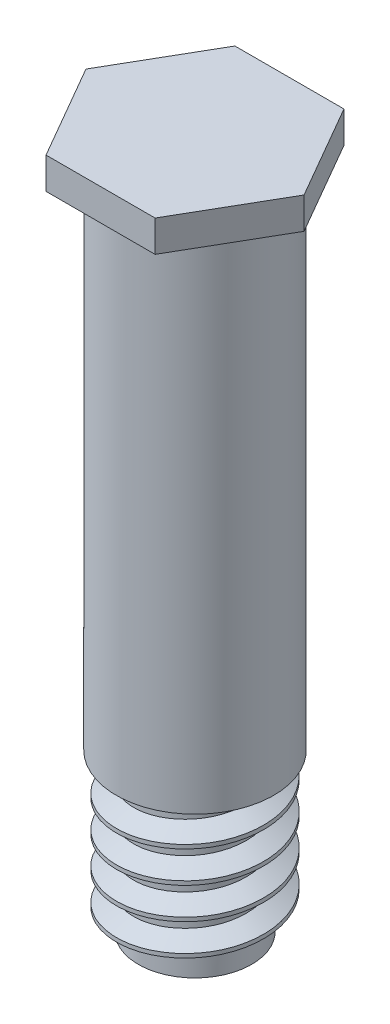
SolidWorks part; units mm, degrees
material "Alumina"
ref_plane "Front Plane" through (0, 0, 0) normal (0, 0, 1) x (1, 0, 0)
ref_plane "Top Plane" through (0, 0, 0) normal (0, 1, 0) x (1, 0, 0)
ref_plane "Right Plane" through (0, 0, 0) normal (1, 0, 0) x (0, 0, -1)
sketch "Sketch1" plane through (0, 0, 0) normal (0, 1, 0) x (1, 0, 0)
  circle A0 centre (0, 0) radius 3.175
  dimension "D1" = 6.35
extrude "Boss-Extrude1" add sketch "Sketch1" along normal blind 26.67
sketch "Sketch2" plane through (0, 26.67, 0) normal (0, 1, 0) x (1, 0, 0)
  line L1 (2.1997, -3.81) -> (4.3994, 0)
  line L2 (4.3994, 0) -> (2.1997, 3.81)
  line L3 (2.1997, 3.81) -> (-2.1997, 3.81)
  line L4 (-2.1997, 3.81) -> (-4.3994, 0)
  line L5 (-4.3994, 0) -> (-2.1997, -3.81)
  line L6 (-2.1997, -3.81) -> (2.1997, -3.81)
  circle A0 centre (0, 0) radius 3.81 construction
  dimension "D1" = 7.62
extrude "Boss-Extrude2" add sketch "Sketch2" along normal blind 1.27
sketch "Sketch6" plane through (0, 0, 0) normal (0, -1, 0) x (1, 0, 0)
  circle A0 centre (0, 0) radius 3.175
  circle A1 centre (0, 0) radius 2.286
  dimension "D1" = 6.35
  dimension "D2" = 4.572
extrude "Cut-Extrude1" cut sketch "Sketch6" against normal blind 6.35
thread "Thread3" pitch 1.27 method extrude profile "Thread Profile3" start angle 0, offset 0, length 5.334, pitch 1.27, diameter 4.572
ref_plane "Plane3" through (-2.286, 6.35, 0) normal (0, 0, 1) x (-1, 0, 0)
sketch "Thread Profile3" plane through (-2.286, 6.35, 0) normal (0, 0, 1) x (-1, 0, 0)
  line L0 (0, 0) -> (0, 1.27) construction
  line L1 (0, 0) -> (0.6874, 0.3969)
  line L2 (0.6874, 0.3969) -> (0.6874, 0.5556)
  line L3 (0.6874, 0.5556) -> (0, 0.9525)
  line L4 (0.6874, 0.4762) -> (0, 0.4762) construction
  line L11 (0, 0) -> (0, 0.9525)
  point P2 (0, 0)
  dimension "Pitch" = 1.27
  dimension "Profile_Angle" = 60
  dimension "Profile_Land" = 0.1588
  dimension "Profile_Height" = 0.6874
